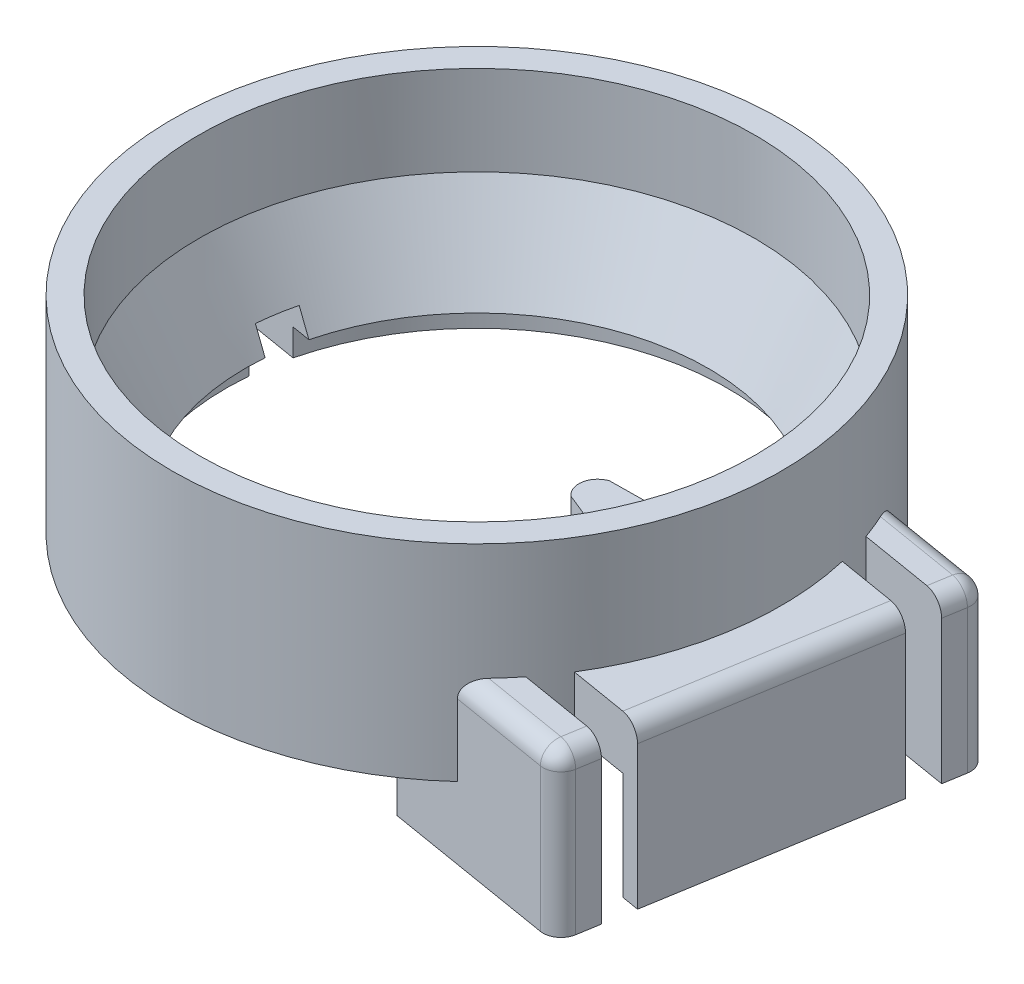
SolidWorks part; units mm, degrees
ref_plane "Front Plane" through (0, 0, 0) normal (0, 0, 1) x (1, 0, 0)
ref_plane "Top Plane" through (0, 0, 0) normal (0, 1, 0) x (1, 0, 0)
ref_plane "Right Plane" through (0, 0, 0) normal (1, 0, 0) x (0, 0, -1)
sketch "Sketch1" plane through (0, 0, 0) normal (0, 0, 1) x (1, 0, 0)
  line L0 (0, 20.4717) -> (0, -21.5283) construction
  line L1 (-28, 3) -> (-28, 0)
  line L2 (-28, 0) -> (-34.0039, 0)
  line L3 (-31.0039, 13) -> (-34.0039, 13)
  line L4 (-28, 3) -> (-25.85, 3)
  line L5 (-25.85, 3) -> (-31.0039, 13)
  line L6 (-34.0039, 13) -> (-34.0039, 0)
  dimension "D1" = 28
  dimension "D2" = 3
  dimension "D3" = 3
  dimension "D4" = 2.15
  dimension "D5" = 10
  dimension "D6" = 11.25
revolve "Revolve1" add sketch "Sketch1" angle 360 about L0
sketch "Sketch3" plane through (-29.4947, 0, -4.9064) normal (-0.9864, 0, -0.1641) x (-0.1641, 0, 0.9864)
  line L1 (-2.125, -5.5547) -> (2.125, -5.5547)
  line L2 (-2.125, -5.5547) -> (-2.125, 5.5547)
  line L3 (-2.125, 5.5547) -> (2.125, 5.5547)
  line L4 (2.125, -5.5547) -> (2.125, 5.5547)
  line L5 (-2.125, -5.5547) -> (2.125, 5.5547) construction
  line L6 (-2.125, 5.5547) -> (2.125, -5.5547) construction
  line L19 (0, 25.8545) -> (0, -45.7829) construction
  point P0 (0, 0)
  dimension "D1" = 4.25
extrude "Cut-Extrude1" cut sketch "Sketch3" against normal blind 11.5 and the other way blind 12.5
ref_plane "Plane1" through (20.6167, 0, 3.4296) normal (0.9864, 0, 0.1641) x (0.1641, 0, -0.9864)
sketch "Sketch4" plane through (20.6167, 0, 3.4296) normal (0.9864, 0, 0.1641) x (0.1641, 0, -0.9864)
  line L1 (-3, 3) -> (3, 3)
  line L2 (-3, 3) -> (-3, 13)
  line L3 (-3, 13) -> (3, 13)
  line L4 (3, 3) -> (3, 13)
  line L5 (-3, 3) -> (3, 13) construction
  line L6 (-3, 13) -> (3, 3) construction
  line L7 (-25.85, 3) -> (25.85, 3) construction
  line L9 (0, -52.2101) -> (0, 25.0312) construction
  point P0 (0, 8)
  dimension "D1" = 6
extrude "Boss-Extrude1" add sketch "Sketch4" along normal up to surface (4.7753 mm away) up to face at (0, 13, 31.0039)
ref_plane "Plane2" through (0, 0, 0) normal (-0.1641, 0, 0.9864) x (0.9864, 0, 0.1641)
ref_plane "Plane3" through (0, 13, 0) normal (0, -1, 0) x (-0.1641, 0, 0.9864)
ref_plane "Plane4" through (35.4134, 0, 5.891) normal (0.9864, 0, 0.1641) x (0.1641, 0, -0.9864)
ref_plane "Plane5" through (0, 10, 0) normal (0, 1, 0) x (1, 0, 0)
sketch "Sketch8" plane through (35.4134, 0, 5.891) normal (0.9864, 0, 0.1641) x (0.1641, 0, -0.9864)
  line L1 (8, 0) -> (16.5, 0)
  line L2 (8, 0) -> (8, 4)
  line L3 (8, 4) -> (13, 4)
  line L4 (16.5, 0) -> (16.5, 4)
  line L5 (-8, 0) -> (-16.5, 0)
  line L6 (-8, 0) -> (-8, 4)
  line L7 (-8, 4) -> (-13, 4)
  line L8 (-16.5, 0) -> (-16.5, 4)
  line L9 (13, 5) -> (16.5, 5)
  line L10 (16.5, 4) -> (16.5, 5)
  line L12 (13, 4) -> (13, 5)
  line L14 (-16.5, 4) -> (-16.5, 5)
  line L16 (-13, 4) -> (-13, 5)
  line L18 (-16.5, 5) -> (-13, 5)
  dimension "D1" = 4
  dimension "D2" = 8.5
  dimension "D3" = 4
  dimension "D4" = 8.5
  dimension "D5" = 16
  dimension "D10" = 8
  dimension "D11" = 1
  dimension "D13" = 1
extrude "Cut-Extrude2" cut sketch "Sketch8" against normal up to surface (12.9506 mm away) up to face at (-6.8265, 6.1387, -1.1356)
sketch "Sketch7" plane through (0, 13, 0) normal (0, -1, 0) x (-0.1641, 0, 0.9864)
  line L0 (-31.24, -20.9) -> (31.24, -20.9) construction
  line L1 (7.148, -23.9469) -> (7.2221, -24.1951)
  line L2 (1.7208, -15.2195) -> (3, -20.9)
  line L3 (-1.9849, -15.2195) -> (-3, -20.9)
  line L4 (-3, -20.9) -> (-3.637, -22.258)
  line L5 (-3, -30.8584) -> (-3, -20.9) construction
  line L6 (3, -30.8584) -> (3, -20.9) construction
  line L7 (-7.1706, -23.9716) -> (-7.2362, -24.1909)
  line L9 (3, -20.9) -> (3.697, -22.2282)
  arc A0 (1.7208, -15.2195) -> (-1.9849, -15.2195) centre (-0.132, -16.2282) ccw
  arc A1 (-7.1706, -23.9716) -> (-3.637, -22.258) centre (-7.1706, -19.4716) ccw
  arc A2 (3.697, -22.2282) -> (7.148, -23.9469) centre (7.2352, -19.4477) ccw
  arc A3 (-7.2362, -24.1909) -> (7.2221, -24.1951) centre (0, 0) ccw
  arc A4 (-8, -24.5809) -> (-3, -25.6753) centre (0, 0) ccw construction
  dimension "D3" = 9
  dimension "D4" = 25.25
  dimension "D5" = 195
  dimension "D2" = 9
  dimension "D7" = 195
  dimension "D6" = 1.5
  dimension "D11" = 1.5
extrude "Boss-Extrude11" add sketch "Sketch7" along normal offset from surface (14 mm away) 1 contours L3 L4 A1 L7 A3 L1 A2 L9 L2 A0 up to face at (-8.1372, 0, 18.5983) offset beyond the face yes
sketch "Sketch11" plane through (0, 10, 0) normal (0, 1, 0) x (1, 0, 0)
  line L0 (113.4679, 2.4133) -> (-53.8888, 30.2529) construction
  line L2 (25.0228, 12.5642) -> (32.0369, 11.3974) construction
  line L3 (29.8279, 16.3267) -> (42.9076, 14.1509)
  line L4 (0, 0) -> (95.4035, -15.8703) construction
  line L5 (42.9076, 14.1509) -> (36.0156, -27.2797)
  line L6 (107.7414, -39.2113) -> (-48.215, -13.268) construction
  line L7 (19.6077, -19.9885) -> (26.6218, -21.1553) construction
  line L8 (22.9359, -25.1039) -> (36.0156, -27.2797)
  line L9 (38.7736, 25.864) -> (21.9562, -75.2327) construction
  circle A0 centre (0, 0) radius 34.0039 construction
  arc A2 (22.9359, -25.1039) -> (29.8279, 16.3267) centre (0, 0) ccw
  dimension "D1" = 4.5
  dimension "D2" = 4.5
  dimension "D3" = 6
extrude "Boss-Extrude13" add sketch "Sketch11" against normal offset from surface (18 mm away) 8 up to face at (30.0585, 0, 5.0002) offset beyond the face yes
sketch "Sketch12" plane through (0, -8, 0) normal (0, -1, 0) x (1, 0, 0)
  line L0 (26.6218, 21.1553) -> (34.7812, 22.5126)
  line L1 (34.7812, 22.5126) -> (36.176, 14.1278)
  line L2 (36.176, 14.1278) -> (31.2887, 13.3148)
  line L3 (33.9142, -2.4683) -> (38.8015, -1.6553)
  line L4 (38.8015, -1.6553) -> (40.1963, -10.0401)
  line L5 (40.1963, -10.0401) -> (32.0369, -11.3974)
  line L6 (36.0156, 27.2797) -> (42.9076, -14.1509) construction
  line L8 (25.0228, -12.5642) -> (32.0369, -11.3974) construction
  line L9 (27.7818, -3.4884) -> (33.9142, -2.4683) construction
  line L10 (25.1563, 12.2947) -> (31.2887, 13.3148) construction
  line L11 (19.6077, 19.9885) -> (26.6218, 21.1553) construction
  arc A0 (32.0369, -11.3974) -> (33.9142, -2.4683) centre (0, 0) ccw
  arc A1 (31.2887, 13.3148) -> (26.6218, 21.1553) centre (0, 0) ccw
  dimension "D1" = 2
  dimension "D2" = 2
extrude "Cut-Extrude4" cut sketch "Sketch12" against normal up to surface (12 mm away) up to face at (29.5337, 4, -5.7537)
sketch "Sketch14" plane through (0, 13, 0) normal (0, 1, 0) x (1, 0, 0)
  line L0 (42.1692, 9.7119) -> (41.5948, 6.2594)
  line L1 (42.1692, 9.7119) -> (32.0369, 11.3974)
  line L2 (41.5948, 6.2594) -> (33.1281, 7.6678)
  line L4 (36.0156, -27.2797) -> (42.9076, 14.1509) construction
  line L5 (36.7541, -22.8407) -> (37.3284, -19.3882)
  line L6 (36.7541, -22.8407) -> (26.6218, -21.1553)
  line L7 (37.3284, -19.3882) -> (28.8616, -17.9797)
  line L10 (19.6077, -19.9885) -> (26.6218, -21.1553) construction
  line L12 (31.2887, -13.3148) -> (36.176, -14.1278) construction
  line L13 (38.8015, 1.6553) -> (33.9142, 2.4683) construction
  line L14 (32.0369, 11.3974) -> (40.1963, 10.0401) construction
  arc A0 (33.1281, 7.6678) -> (32.0369, 11.3974) centre (0, 0) ccw
  arc A1 (26.6218, -21.1553) -> (28.8616, -17.9797) centre (0, 0) ccw
  dimension "D3" = 68.0078
  dimension "D1" = 0
  dimension "D2" = 5
  dimension "D5" = 5
  dimension "D6" = 0
extrude "Cut-Extrude5" cut sketch "Sketch14" against normal up to surface (21 mm away) up to face at (33.8851, -8, 5.6368)
fillet "Fillet1" radius 2 7 edges at (36.3848, 10, 25.0602) (36.0156, 1, 27.2797) (42.9076, 1, -14.1509) (36.3677, 10, -15.2388) (42.5384, 10, -11.9314) (39.4616, 10, 6.5644) (29.4758, 10, 26.1918)
sketch "Sketch15" plane through (0, 0, 0) normal (0, -1, 0) x (1, 0, 0)
  line L0 (32.0369, -11.3974) -> (25.0228, -12.5642)
  line L1 (29.8279, -16.3267) -> (21.7152, -17.6763)
  line L2 (26.6218, 21.1553) -> (19.6077, 19.9885)
  line L3 (22.9359, 25.1039) -> (14.8232, 23.7544)
  line L4 (22.9359, 25.1039) -> (34.0427, 26.9516) construction
  arc A0 (21.7152, -17.6763) -> (25.0228, -12.5642) centre (0, 0) ccw
  arc A1 (19.6077, 19.9885) -> (14.8232, 23.7544) centre (0, 0) ccw
  arc A2 (29.8279, -16.3267) -> (32.0369, -11.3974) centre (0, 0) ccw
  arc A3 (26.6218, 21.1553) -> (22.9359, 25.1039) centre (0, 0) ccw
extrude "Boss-Extrude14" add sketch "Sketch15" along normal up to surface (8 mm away) up to face at (37.6245, -8, -12.8956)
sketch "Sketch16" plane through (0, -8, 0) normal (0, -1, 0) x (1, 0, 0)
  line L0 (33.9142, -2.4683) -> (31.2887, 13.3148)
  line L1 (33.9142, -2.4683) -> (37.86, -1.812)
  line L2 (31.2887, 13.3148) -> (35.2344, 13.9712)
  line L3 (37.86, -1.812) -> (35.2344, 13.9712)
  arc A0 (33.9142, -2.4683) -> (31.2887, 13.3148) centre (0, 0) ccw construction
  dimension "D1" = 4
extrude "Cut-Extrude6" cut sketch "Sketch16" against normal up to surface (8 mm away) up to face at (30.0585, 0, 5.0002)
sketch "Sketch17" plane through (0, 13, 0) normal (0, 1, 0) x (1, 0, 0)
  circle A0 centre (0, 0) radius 31.0039
  circle A1 centre (0, 0) radius 34.0039
extrude "Boss-Extrude15" add sketch "Sketch17" along normal blind 10
